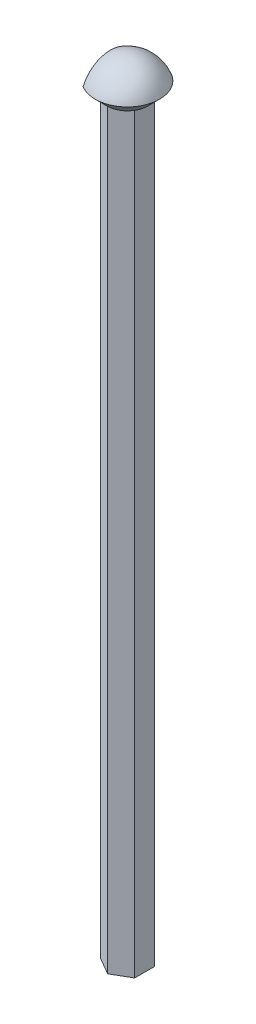
SolidWorks part; units mm, degrees
ref_plane "Front Plane" through (0, 0, 0) normal (0, 0, 1) x (1, 0, 0)
ref_plane "Top Plane" through (0, 0, 0) normal (0, 1, 0) x (1, 0, 0)
ref_plane "Right Plane" through (0, 0, 0) normal (1, 0, 0) x (0, 0, -1)
sketch "Sketch1" plane through (0, 0, 0) normal (0, 1, 0) x (1, 0, 0)
  line L1 (0, 3.6662) -> (-3.175, 1.8331)
  line L2 (-3.175, 1.8331) -> (-3.175, -1.8331)
  line L3 (-3.175, -1.8331) -> (0, -3.6662)
  line L4 (0, -3.6662) -> (3.175, -1.8331)
  line L5 (3.175, -1.8331) -> (3.175, 1.8331)
  line L6 (3.175, 1.8331) -> (0, 3.6662)
  circle A0 centre (0, 0) radius 3.175 construction
  dimension "D1" = 6.35
extrude "Boss-Extrude1" add sketch "Sketch1" along normal blind 139.7
sketch "Sketch3" plane through (0, 139.7, 0) normal (0, 1, 0) x (1, 0, 0)
  circle A0 centre (0, 0) radius 6.35
  dimension "D1" = 12.7
extrude "Boss-Extrude2" add sketch "Sketch3" along normal blind 6.35
fillet "Fillet1" radius 6.35 1 edges at (0, 146.05, 6.35)
chamfer "Chamfer1" distance 2.54 angle 45 1 edges at (0, 139.7, 6.35)
sketch "Sketch4" plane through (0, 0, 0) normal (0, -1, 0) x (1, 0, 0)
  line L1 (-3.175, -9.7214) -> (-12.8474, -9.7214)
  line L2 (-3.175, -9.7214) -> (-3.175, 12.3647)
  line L3 (-3.175, 12.3647) -> (-12.8474, 12.3647)
  line L4 (-12.8474, -9.7214) -> (-12.8474, 12.3647)
extrude "Cut-Extrude1" cut sketch "Sketch4" against normal blind 152.4
